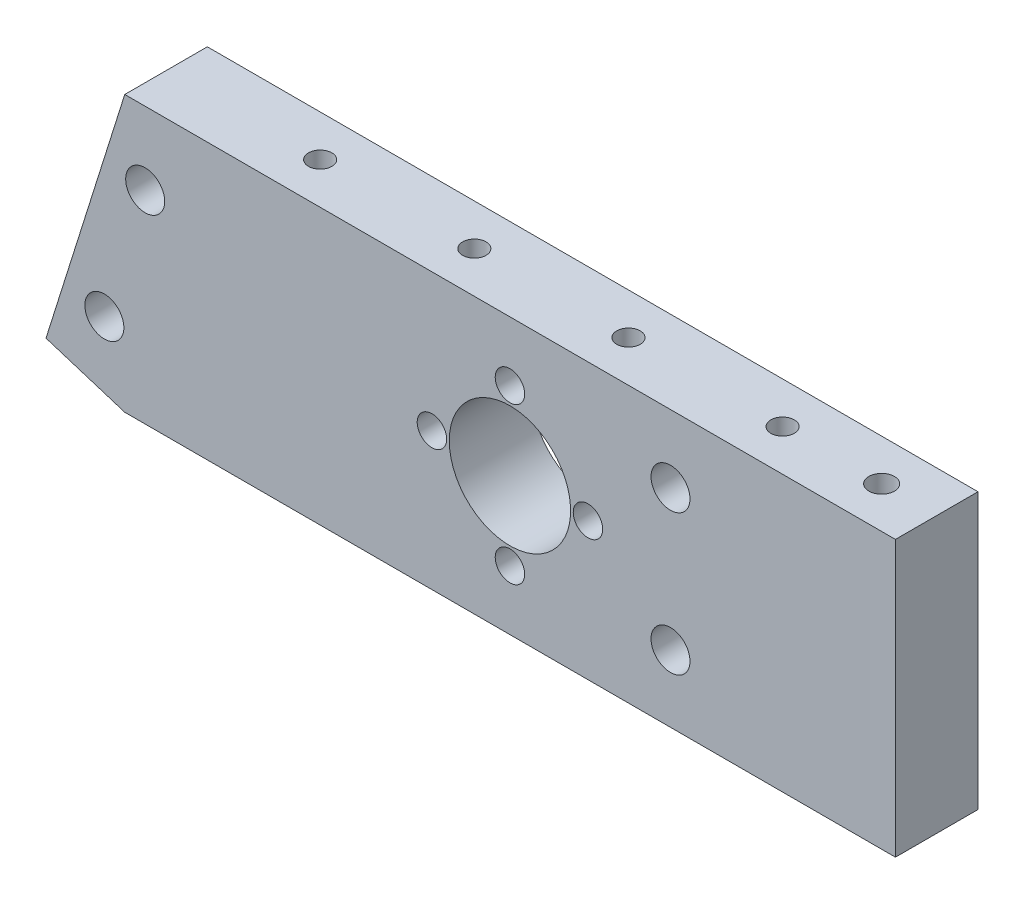
SolidWorks part; units mm, degrees
material "PE High Density"
ref_plane "Front Plane" through (0, 0, 0) normal (0, 0, 1) x (1, 0, 0)
ref_plane "Top Plane" through (0, 0, 0) normal (0, 1, 0) x (1, 0, 0)
ref_plane "Right Plane" through (0, 0, 0) normal (1, 0, 0) x (0, 0, -1)
sketch "Sketch1" plane through (0, 0, 0) normal (0, 0, 1) x (1, 0, 0)
  line L1 (-44.433, 15.875) -> (44.467, 15.875)
  line L3 (-44.433, -15.875) -> (44.467, -15.875)
  line L5 (18.5214, 15.875) -> (18.5214, -15.875) construction
  line L6 (0, 0) -> (44.467, 0) construction
  line L10 (-44.433, 15.875) -> (-53.5192, -13.0175)
  line L12 (0.017, -15.875) -> (0.017, 75.0464) construction
  line L13 (0.017, -15.875) -> (147.1451, -15.875) construction
  line L14 (-44.433, -15.875) -> (-44.433, 15.875) construction
  line L15 (44.467, 15.875) -> (44.467, -15.875)
  line L17 (-44.433, -15.875) -> (-53.5192, -13.0175)
  line L22 (-90.4237, 20.5209) -> (-90.4237, -9.9591) construction
  line L23 (-48.9761, -14.4463) -> (-39.4405, 15.875) construction
  line L25 (-44.433, 15.875) -> (-28.8763, 10.9827) construction
  circle A2 centre (0, 9) radius 1.7 construction
  arc A8 (-5.3578, -2.967) -> (-5.3172, -2.9531) centre (-6.35, 0) ccw construction
  circle A16 centre (0, 0) radius 7 construction
  circle A17 centre (0, 0) radius 9 construction
  circle A18 centre (18.5214, 8.0606) radius 2.2479
  circle A19 centre (18.5211, -8.1496) radius 2.2479
  circle A20 centre (9, 0) radius 1.7 construction
  circle A21 centre (0, -9) radius 1.7 construction
  circle A22 centre (-9, 0) radius 1.7 construction
  circle A23 centre (-90.4237, -2.6566) radius 2.2479 construction
  circle A24 centre (-90.4237, 13.2184) radius 2.2479 construction
  circle A25 centre (-42.0798, 7.4825) radius 2.25
  circle A26 centre (-46.7861, -7.4825) radius 2.25
  circle A27 centre (0, -9) radius 1.7
  circle A28 centre (-9, 0) radius 1.7
  circle A29 centre (0, 9) radius 1.7
  circle A30 centre (9, 0) radius 1.7
  circle A43 centre (0, 0) radius 7
  point P0 (0, 0)
  point P27 (0, 0)
  point P44 (0, 0)
  dimension "D5" = 14
  dimension "D7" = 4.4958
  dimension "D12" = 18.0001
  dimension "D3" = 3.4
  dimension "D20" = 4.4958
  dimension "D21" = 4.4958
  dimension "D23" = 4.5
  dimension "D25" = 4.5
  dimension "D8" = 88.9
  dimension "D17" = 88.9
  dimension "D2" = 90
  dimension "D10" = 31.75
  dimension "D4" = 90
  dimension "D9" = 90
  dimension "D11" = 44.467
  dimension "D13" = 90
  dimension "D15" = 30.48
  dimension "D16" = 7.3025
  dimension "D18" = 7.3025
  dimension "D22" = 90
  dimension "D14" = 9.525
  dimension "D19" = 4.7625
  dimension "D24" = 7.3
  dimension "D26" = 7.3
  dimension "D27" = 7.8144
  dimension "D28" = 7.7254
  dimension "D6" = 4
extrude "Boss-Extrude1" add sketch "Sketch1" along normal blind 9.525
hole_wizard "Tap Drill for #6-32 Tap1" positions "Sketch11" profile "Sketch12" hole size "#6-32" standard "ANSI Inch"
sketch "Sketch11" plane through (0, -15.875, 0) normal (0, -1, 0) x (-1, 0, 0)
  line L0 (-44.467, -9.525) -> (-44.467, 0) construction
  line L1 (44.433, -9.525) -> (-44.467, -9.525) construction
  point P0 (-26.687, -4.7625)
  dimension "D1" = 17.78
  dimension "D2" = 4.7625
sketch "Sketch12" plane through (26.687, -15.875, 4.7625) normal (1, 0, 0) x (0, 0, -1)
  line L0 (0, 0) -> (0, 13.5127)
  line L1 (0, 13.5127) -> (1.3525, 12.7)
  line L2 (1.3525, 12.7) -> (1.3525, 0)
  line L5 (1.3525, 0) -> (0, 0)
  line L10 (0, 13.5127) -> (-1.3526, 12.7) construction
  line L11 (0, -6.35) -> (0, 107.95) construction
  dimension "Hole Dia." = 2.7051
  dimension "Hole Depth" = 12.7
  dimension "Drill Angle" = 118
pattern_linear "LPattern1" count 4 spacing 17.78 along (-1, 0, 0) of "Tap Drill for #6-32 Tap1"
mirror "Mirror8" about plane through (0, 0, 0) normal (0, 1, 0) of "Tap Drill for #6-32 Tap1", "LPattern1"
sketch "Sketch13" plane through (0, -15.875, 0) normal (0, -1, 0) x (1, 0, 0)
  line L0 (38.117, 9.525) -> (38.117, 0) construction
  line L1 (-44.433, 9.525) -> (44.467, 9.525) construction
  line L2 (-44.433, 0) -> (44.467, 0) construction
  line L3 (44.467, 9.525) -> (44.467, 0) construction
  circle A0 centre (38.117, 4.7625) radius 1.4732
  dimension "D2" = 2.9464
  dimension "D1" = 6.35
extrude "Cut-Extrude1" cut sketch "Sketch13" against normal blind 12.7
mirror "Mirror9" about plane through (0, 0, 0) normal (0, 1, 0) of "Cut-Extrude1"
equation "\"Plate Screw Hole Diameter\"= 0.116in"
equation "\"Plate Width\" = 3.5in"
equation "\"Plate Thickness\" = 0.375in"
equation "\"Num holes\" = 4"
equation "\"Plate Height\" = 1.25in"
equation "\"D1@Sketch11\"=\"Plate Width\" / ( \"Num holes\" + 1)"
equation "\"D2@Sketch11\"=\"Plate Thickness\"/2"
equation "\"D3@LPattern1\"=\"Plate Width\" / ( \"Num holes\"  + 1 )"
equation "\"Top Plate Width\" = 4.5in"
equation "\"D8@Sketch1\"=\"Plate Width\""
equation "\"Plate Clearance Hole Diameter\" = 0.125in"
equation "\"Plate Tap Hole Diameter\" = 0.116in"
equation "\"Bottom Plate Length\" = 6.5in"
equation "\"Number Eight Clearance Size\" = 0.177in"
equation "\"D7@Sketch1\"=\"Number Eight Clearance Size\""
equation "\"back_brace_height_offset\"=0.35"
equation "\"D2@Sketch13\"=\"Plate Tap Hole Diameter\""
equation "\"D17@Sketch1\"=\"Plate Width\""
equation "\"D10@Sketch1\"=\"Plate Height\""
